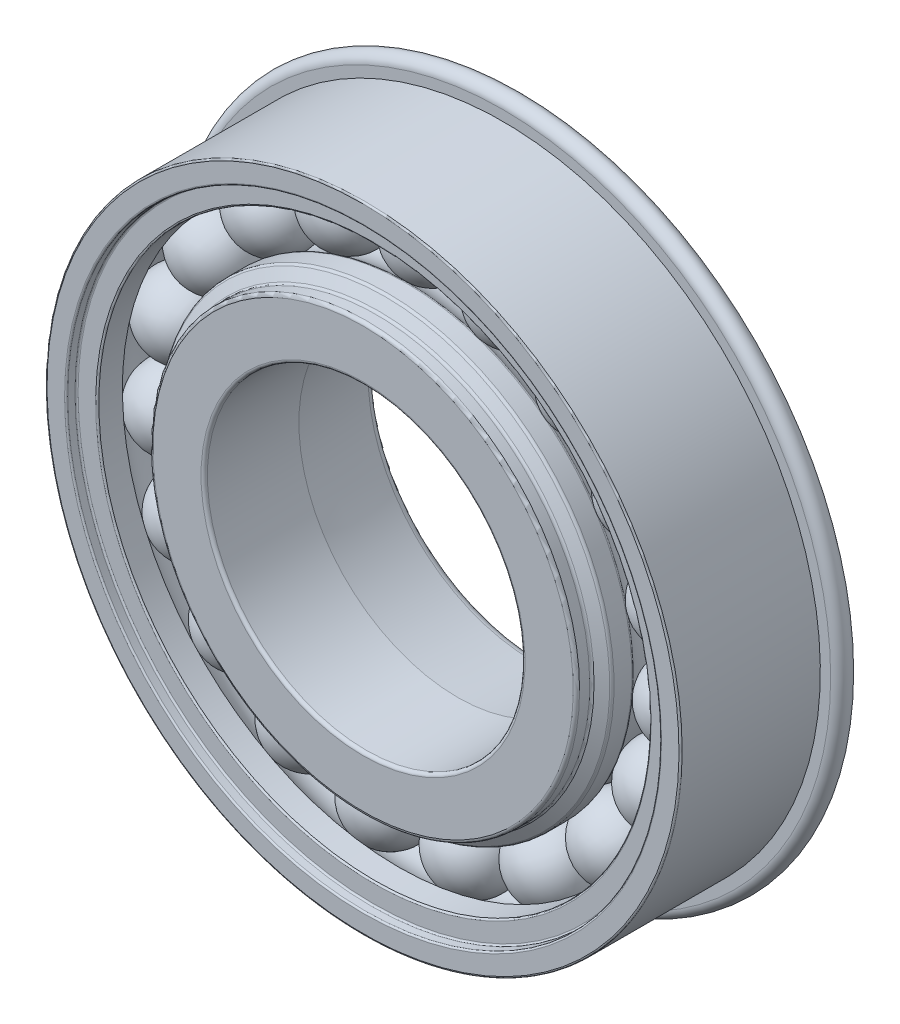
SolidWorks part; units mm, degrees
ref_plane "Front Plane" through (0, 0, 0) normal (0, 0, 1) x (1, 0, 0)
ref_plane "Top Plane" through (0, 0, 0) normal (0, 1, 0) x (1, 0, 0)
ref_plane "Right Plane" through (0, 0, 0) normal (1, 0, 0) x (0, 0, -1)
sketch "Sketch1" plane through (0, 0, 0) normal (1, 0, 0) x (0, 0, -1)
  line L0 (-7.1501, 0) -> (7.1501, 0) construction
  line L1 (5.5499, 0) -> (5.5499, 26.9875)
  line L2 (5.5499, 26.9875) -> (4.0259, 26.9875)
  line L3 (4.0259, 26.9875) -> (4.0259, 25.4)
  line L4 (4.0259, 25.4) -> (-7.1501, 25.4)
  line L5 (-7.1501, 12.7) -> (5.5499, 12.7)
  line L6 (-7.1501, 17.0688) -> (7.1501, 17.0688)
  line L7 (-1.5621, 25.4) -> (-1.5621, 19.05) construction
  arc A0 (4.0259, 26.2255) -> (5.5499, 26.2255) centre (4.7879, 26.2255) cw
  point P4 (0, 0)
  dimension "Inner Ring Width" = 14.3002
  dimension "Flange OD" = 53.975
  dimension "OD" = 50.8
  dimension "Width" = 12.7
  dimension "ID" = 25.4
  dimension "Inner Ring OD" = 34.1376
  dimension "Flange Thickness" = 1.524
  dimension "Ball Diameter" = 6.35
  dimension "For Shaft Diameter" = 25.4
  dimension "For Housing ID" = 50.8
sketch "Sketch2" plane through (0, 0, 0) normal (1, 0, 0) x (0, 0, -1)
  line L0 (4.0259, 25.4) -> (-7.1501, 25.4) construction
  line L1 (4.0259, 25.4) -> (-7.1501, 25.4)
  line L2 (4.0259, 25.4) -> (4.0259, 26.2255)
  line L3 (5.5499, 26.2255) -> (5.5499, 22.0853)
  line L4 (5.5499, 0) -> (5.5499, 26.9875) construction
  line L5 (5.5499, 22.0853) -> (1.1875, 22.0853)
  line L6 (-6.3214, 22.0853) -> (-6.3214, 23.7427)
  line L7 (-6.3214, 23.7427) -> (-7.1501, 23.7426)
  line L8 (-7.1501, 23.7426) -> (-7.1501, 25.4)
  line L9 (-1.5621, 23.6728) -> (-1.5621, 25.4) construction
  line L10 (-1.5621, 12.7) -> (-1.5621, 14.8844) construction
  line L11 (-1.5621, 14.8844) -> (-1.5621, 17.0688) construction
  line L12 (-7.1501, 17.0688) -> (7.1501, 17.0688) construction
  line L13 (-7.1501, 12.7) -> (5.5499, 12.7) construction
  line L14 (-1.5621, 23.6728) -> (-1.5621, 22.0853) construction
  line L15 (-1.5621, 22.0853) -> (-1.5621, 20.4978) construction
  line L16 (-4.3117, 22.0853) -> (-6.3214, 22.0853)
  line L17 (-5.4928, 23.7426) -> (-7.1501, 23.7426) construction
  arc A0 (5.5499, 26.2255) -> (4.0259, 26.2255) centre (4.7879, 26.2255) ccw construction
  arc A1 (5.5499, 26.2255) -> (4.0259, 26.2255) centre (4.7879, 26.2255) ccw
  circle A2 centre (-1.5621, 20.4978) radius 3.175 construction
  arc A3 (-4.3117, 22.0853) -> (1.1875, 22.0853) centre (-1.5621, 20.4978) cw
  point P10 (-1.5621, 25.4)
  point P12 (-1.5621, 17.3228)
  point P23 (-1.5621, 17.0688)
  point P24 (-1.5621, 22.0853)
  point P33 (-6.3214, 23.7427)
  dimension "D1" = 6.35
  dimension "D2" = 0.254
revolve "Revolve1" add sketch "Sketch2" angle 360 about L0
sketch "Sketch3" plane through (0, 0, 0) normal (1, 0, 0) x (0, 0, -1)
  line L0 (-7.1501, 17.0688) -> (7.1501, 17.0688) construction
  line L1 (-7.1501, 17.0688) -> (-5.9403, 17.0688)
  line L2 (7.1501, 17.0688) -> (7.1501, 12.7)
  line L3 (7.1501, 12.7) -> (-7.1501, 12.7)
  line L4 (-7.1501, 12.7) -> (-7.1501, 17.0688)
  line L5 (4.0259, 17.0688) -> (7.1501, 17.0688)
  line L6 (-5.9403, 17.0688) -> (-5.3353, 18.1165)
  line L7 (-5.3353, 18.1165) -> (-3.6622, 18.1166)
  line L8 (0.538, 18.1166) -> (3.421, 18.1165)
  line L9 (3.421, 18.1165) -> (4.0259, 17.0688)
  line L10 (-1.5621, 20.4978) -> (-1.5621, 18.9103) construction
  line L11 (-1.5621, 18.9103) -> (-1.5621, 17.3228) construction
  circle A2 centre (-1.5621, 20.4978) radius 3.175 construction
  arc A3 (-3.6622, 18.1166) -> (0.538, 18.1166) centre (-1.5621, 20.4978) ccw
  point P12 (-1.5621, 18.1166)
  dimension "D1" = 60
  dimension "D2" = 60
revolve "Revolve2" add sketch "Sketch3" angle 360 about L0
sketch "Sketch5" plane through (0, 0, 0) normal (1, 0, 0) x (0, 0, -1)
  line L0 (7.1501, 13.7922) -> (7.1501, 12.7)
  line L2 (6.4805, 13.2303) -> (0.4189, 12.7)
  line L8 (6.9048, 13.8579) -> (7.1501, 13.7922) construction
  line L12 (7.1501, 17.0688) -> (7.1501, 12.7) construction
  line L13 (7.1501, 13.7922) -> (7.1501, 14.8844) construction
  line L14 (7.1501, 12.7) -> (-7.1501, 12.7) construction
  line L15 (0.4189, 12.7) -> (7.1501, 12.7)
  arc A0 (7.1501, 13.7922) -> (6.4805, 13.2303) centre (6.4141, 13.9894) cw
  dimension "D3" = 0.762
  dimension "D1" = 105
  dimension "D2" = 0.254
  dimension "D4" = 5
revolve "Cut-Revolve2" cut sketch "Sketch5" angle 360 about L0
sketch "Sketch6" plane through (0, 0, 0) normal (1, 0, 0) x (0, 0, -1)
  line L0 (6.9048, 13.8579) -> (7.1501, 13.7922) construction
  line L1 (6.9048, 13.8579) -> (7.1501, 13.7922)
  line L2 (6.9048, 13.8579) -> (7.1501, 14.7736) construction
  line L3 (7.1501, 17.0688) -> (7.1501, 12.7) construction
  line L4 (7.1501, 14.7736) -> (7.1501, 13.7922) construction
  line L5 (6.4583, 13.4834) -> (5.5499, 13.4039)
  line L6 (5.5499, 0) -> (5.5499, 26.9875) construction
  line L7 (6.4805, 13.2303) -> (0.4189, 12.7) construction
  line L8 (5.5499, 13.4039) -> (5.5499, 13.5314)
  line L9 (6.7821, 13.8908) -> (7.1501, 13.8908)
  line L10 (6.4473, 13.6099) -> (5.5499, 13.5314)
  line L11 (7.1501, 13.8908) -> (7.1501, 13.7922)
  arc A1 (6.9048, 13.8579) -> (6.4583, 13.4834) centre (6.4141, 13.9894) cw
  arc A2 (6.4473, 13.6099) -> (6.7821, 13.8908) centre (6.4141, 13.9894) ccw
  arc A3 (6.4805, 13.2303) -> (7.1501, 13.7922) centre (6.4141, 13.9894) ccw construction
  dimension "D1" = 0.127
revolve "Cut-Revolve3" cut sketch "Sketch6" angle 360 about L0
fillet "Fillet4" radius 0.762 1 edges at (0, -13.8908, -7.1501)
sketch "Sketch7" plane through (0, 0, 0) normal (1, 0, 0) x (0, 0, -1)
  line L0 (7.1501, 14.8844) -> (7.1501, 15.9766) construction
  line L1 (7.1501, 17.0688) -> (7.1501, 12.7) construction
  line L2 (7.1501, 15.9766) -> (7.1501, 17.0688) construction
  line L3 (7.1501, 15.9766) -> (7.1501, 17.0688)
  line L4 (7.1501, 17.0688) -> (6.786, 17.0688)
  line L5 (-7.1501, 17.0688) -> (7.1501, 17.0688) construction
  line L6 (6.786, 17.0688) -> (6.786, 16.7047)
  line L7 (6.786, 16.7047) -> (6.786, 16.3407)
  line L8 (6.786, 16.3407) -> (6.786, 15.9766)
  line L9 (6.786, 15.9766) -> (7.1501, 15.9766)
revolve "Cut-Revolve4" cut sketch "Sketch7" angle 360 about L0
sketch "Sketch11" plane through (0, 0, 0) normal (1, 0, 0) x (0, 0, -1)
  line L0 (-1.5621, 23.6728) -> (-1.5621, 17.3228)
  circle A0 centre (-1.5621, 20.4978) radius 3.175 construction
  arc A1 (-1.5621, 17.3228) -> (-1.5621, 23.6728) centre (-1.5621, 20.4978) ccw
revolve "Revolve3" add sketch "Sketch11" angle 360 about L0
pattern_circular "CirPattern3" count 19 over 360 about axis through (0, 0, 7.1501) along (0, 0, -1) of bodies 111
fillet "Fillet2" radius 0.127 2 edges at (0, -23.7427, 6.3214) (0, -22.0853, 6.3214)
fillet "Fillet3" radius 0.127 2 edges at (0, -25.4, 7.1501) (0, -23.7426, 7.1501)
fillet "Fillet5" radius 0.254 9 edges at (0, -17.0688, -6.786) (0, -17.0688, -4.0259) (0, -18.1166, -0.538) (0, -18.1166, 3.6622) (0, -18.1165, 5.3353) (0, -17.0688, 5.9403) (0, -17.0688, 7.1501) (0, -12.7, 7.1501) (0, -15.9766, -7.1501)
sketch "Sketch12" plane through (0, 0, -5.5499) normal (0, 0, -1) x (-1, 0, 0)
  line L0 (0, 22.0853) -> (0, 26.2255) construction
  circle A0 centre (0, 0) radius 22.0853 construction
  circle A1 centre (0, 0) radius 22.0853
  circle A2 centre (0, 0) radius 26.2255 construction
  circle A3 centre (0, 0) radius 24.1554
  point P8 (0, 24.1554)
extrude "Cut-Extrude1" cut sketch "Sketch12" against normal blind 1.143
sketch "Sketch13" plane through (0, 0, 0) normal (0, 0, 1) x (1, 0, 0)
  circle A0 centre (0, 0) radius 17.0688
  circle A1 centre (0, 0) radius 26.9875
  circle A2 centre (0, 0) radius 25.4
  circle A3 centre (0, 0) radius 12.7
  point P0 (0, 17.0688)
  point P5 (0, 26.9875)
  point P8 (0, 25.4)
  point P11 (0, 12.7)
equation "\"D1@Sketch2\"=\"Ball Diameter@Sketch1\""
equation "\"D1@Cut-Extrude1\"=\"Flange Thickness@Sketch1\"*.75"
